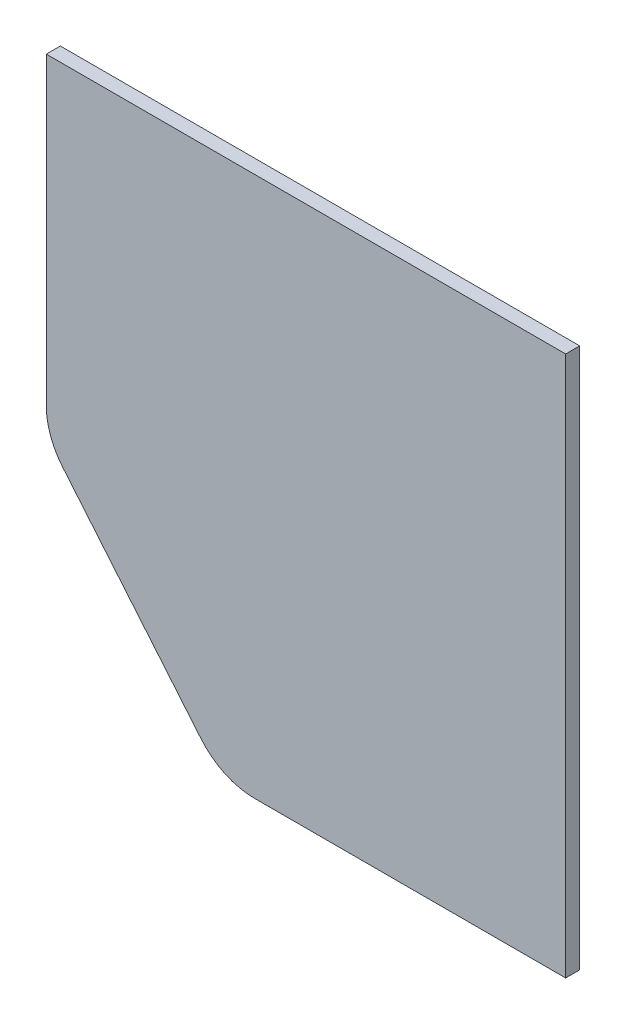
SolidWorks part; units mm, degrees
ref_plane "Plano frontal" through (0, 0, 0) normal (0, 0, 1) x (1, 0, 0)
ref_plane "Plano superior" through (0, 0, 0) normal (0, 1, 0) x (1, 0, 0)
ref_plane "Plano direito" through (0, 0, 0) normal (1, 0, 0) x (0, 0, -1)
sketch "Esboço1" plane through (0, 0, 0) normal (0, 0, 1) x (1, 0, 0)
  line L1 (-86.1657, 44.0263) -> (-12.1657, 44.0263)
  line L2 (-86.1657, 44.0263) -> (-86.1657, -32.9737)
  line L3 (-86.1657, -32.9737) -> (-12.1657, -32.9737)
  line L4 (-12.1657, 44.0263) -> (-12.1657, -32.9737)
  dimension "D1" = 77
  dimension "D2" = 74
extrude "Ressalto-extrusão1" add sketch "Esboço1" along normal blind 2
sketch "Esboço2" plane through (0, 0, 2) normal (0, 0, 1) x (1, 0, 0)
  line L0 (-61.1657, -32.9737) -> (-86.1657, -2.9737)
  line L1 (-86.1657, -32.9737) -> (-12.1657, -32.9737) construction
  line L2 (-86.1657, 44.0263) -> (-86.1657, -32.9737) construction
  dimension "D1" = 25
  dimension "D2" = 30
extrude "Corte-extrusão1" cut sketch "Esboço2" against normal through all and the other way through all
fillet "Filete1" radius 10 1 edges at (-86.1657, -2.9737, 1) type face fillet first side face at (-86.1657, 20.5263, 1) second side face at (-73.6657, -17.9737, 1)
fillet "Filete2" radius 10 1 edges at (-61.1657, -32.9737, 1) type face fillet first side face at (-72.5068, -19.3644, 1) second side face at (-36.6657, -32.9737, 1)
